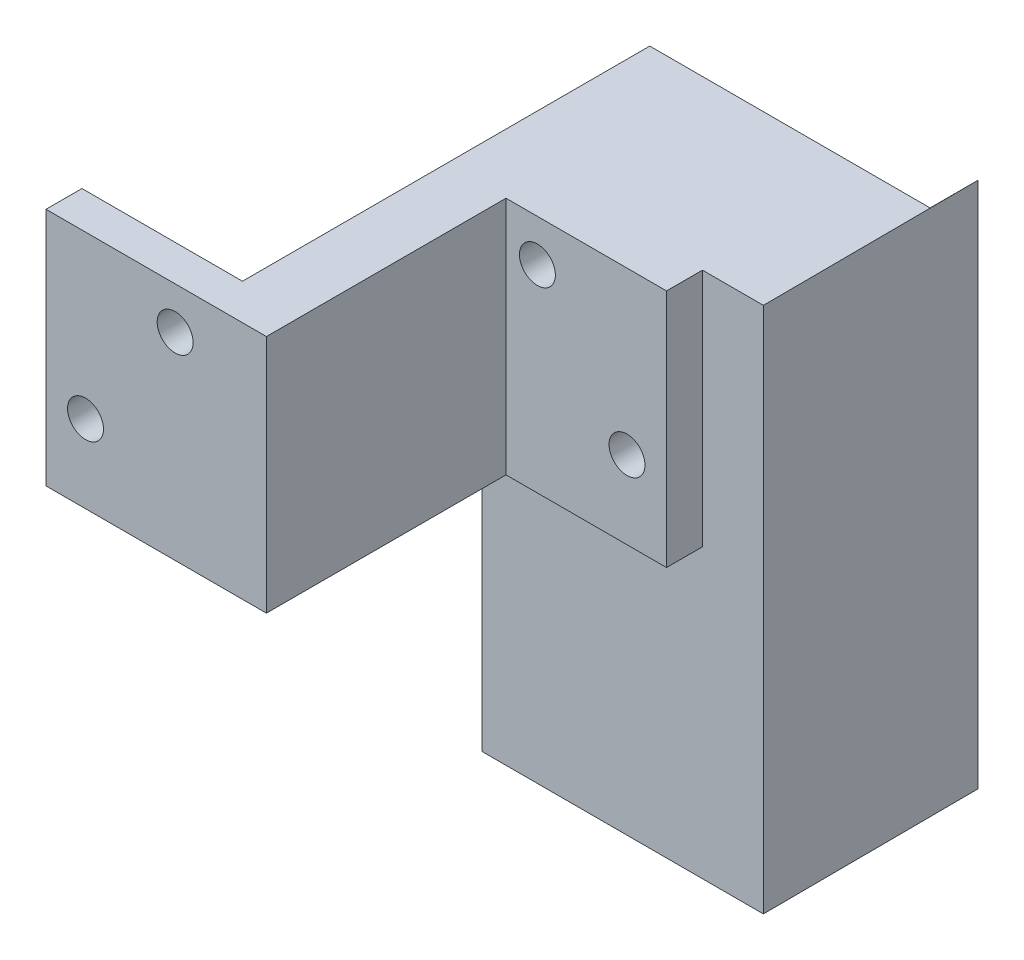
SolidWorks part; units mm, degrees
ref_plane "Front Plane" through (0, 0, 0) normal (0, 0, 1) x (1, 0, 0)
ref_plane "Top Plane" through (0, 0, 0) normal (0, 1, 0) x (1, 0, 0)
ref_plane "Right Plane" through (0, 0, 0) normal (1, 0, 0) x (0, 0, -1)
sketch "Sketch1" plane through (0, 0, 0) normal (0, 1, 0) x (1, 0, 0)
  line L0 (0, 0) -> (18.4, 0)
  line L1 (18.4, 0) -> (18.4, 20)
  line L2 (18.4, 20) -> (31.8, 20)
  line L3 (31.8, 20) -> (31.8, 23)
  line L4 (31.8, 23) -> (13.4, 23)
  line L5 (13.4, 23) -> (13.4, 3)
  line L6 (13.4, 3) -> (0, 3)
  line L7 (0, 3) -> (0, 0)
  dimension "D1" = 13.4
  dimension "D2" = 5
  dimension "D3" = 3
  dimension "D4" = 17
extrude "Boss-Extrude1" add sketch "Sketch1" along normal blind 20
sketch "Sketch2" plane through (0, 0, -20) normal (0, 0, 1) x (1, 0, 0)
  line L1 (31.8, 20) -> (31.8, 0) construction
  line L3 (18.4, 0) -> (31.8, 0) construction
  circle A0 centre (21.02, 16.5) radius 1.5
  circle A1 centre (28.5, 6.5) radius 1.5
  dimension "D1" = 3
  dimension "D2" = 16.5
  dimension "D3" = 10.78
  dimension "D4" = 3.3
  dimension "D5" = 6.5
extrude "Cut-Extrude1" cut sketch "Sketch2" against normal through all both and the other way through all
ref_plane "Plane1" through (15.9, 0, 0) normal (-1, 0, 0) x (0, 0, 1)
mirror "Mirror1" about plane through (15.9, 0, 0) normal (-1, 0, 0) of "Cut-Extrude1"
sketch "Sketch3" plane through (13.4, 0, 0) normal (-1, 0, 0) x (0, 0, 1)
  line L0 (-23, 20) -> (-23, -24)
  line L1 (-23, -24) -> (-41, -24)
  line L2 (-41, -24) -> (-37, 8)
  line L3 (-37, 8) -> (-37, 20)
  line L4 (-37, 20) -> (-23, 20)
  line L5 (-23, 0) -> (-3, 0) construction
  line L6 (-31, -9) -> (-31, -19) construction
  line L7 (-28.45, -9) -> (-28.45, -19)
  line L8 (-33.55, -9) -> (-33.55, -19)
  arc A0 (-28.45, -9) -> (-33.55, -9) centre (-31, -9) ccw
  arc A1 (-33.55, -19) -> (-28.45, -19) centre (-31, -19) ccw
  point P10 (-31, -14)
  dimension "D1" = 12
  dimension "D2" = 14
  dimension "D3" = 24
  dimension "D4" = 18
  dimension "D5" = 10
  dimension "D6" = 5.1
  dimension "D7" = 8
  dimension "D8" = 5
extrude "Boss-Extrude2" add sketch "Sketch3" against normal offset from surface (23.4 mm away) 5 up to face at (31.8, 10, -21.5) offset beyond the face yes
sketch "Sketch4" plane through (0, -24, 0) normal (0, -1, 0) x (1, 0, 0)
  line L2 (36.8, -41) -> (36.8, -23)
  line L5 (36.8, -41) -> (36.8858, -23)
  line L6 (36.8858, -23) -> (36.8, -23)
  dimension "D1" = 0.273
extrude "Boss-Extrude3" add sketch "Sketch4" against normal up to surface (44 mm away) up to face at (20.08, 20, -16.6)
